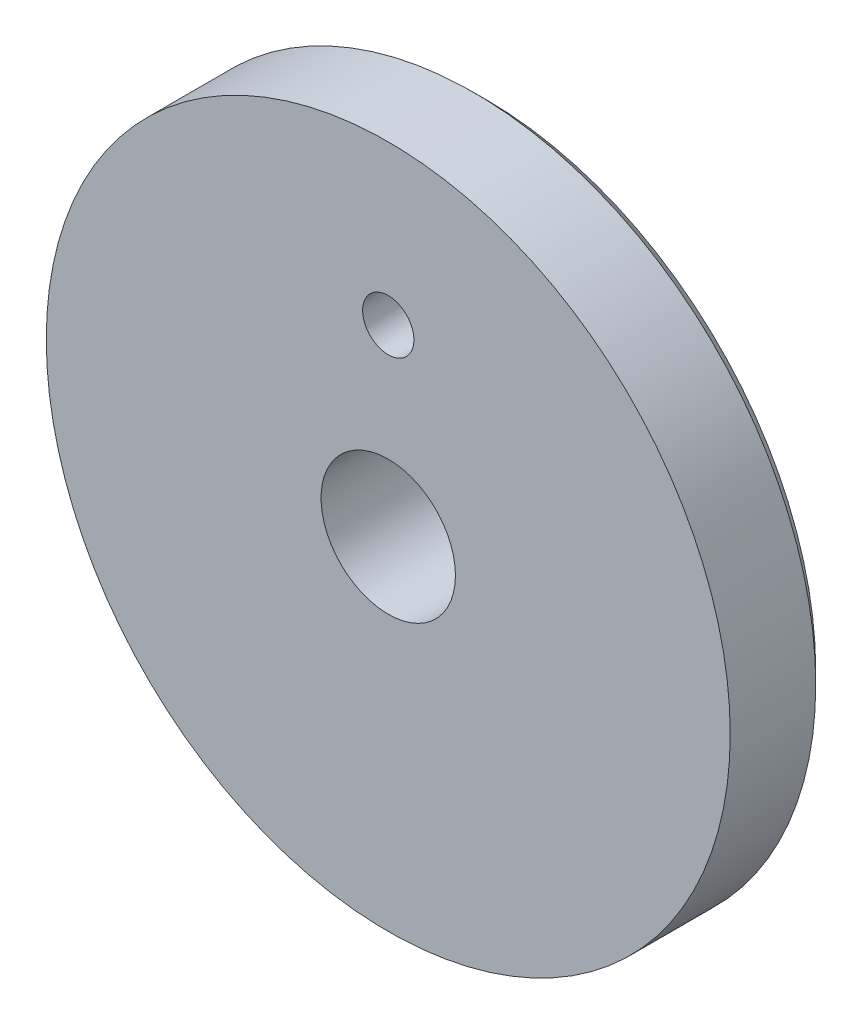
SolidWorks part; units mm, degrees
ref_plane "Front" through (0, 0, 0) normal (0, 0, 1) x (1, 0, 0)
ref_plane "Top" through (0, 0, 0) normal (0, 1, 0) x (1, 0, 0)
ref_plane "Right" through (0, 0, 0) normal (1, 0, 0) x (0, 0, -1)
sketch "Sketch1" plane through (0, 0, 0) normal (0, 0, 1) x (1, 0, 0)
  circle A0 centre (0, 0) radius 14
  circle A1 centre (0, 0) radius 2.75
  dimension "d" = 5.5
  dimension "D0" = 28
extrude "Base-Extrude" add sketch "Sketch1" against normal blind 4
sketch "Sketch2" plane through (7.2492, 0.3213, -4) normal (0, 0, -1) x (-1, 0, 0)
  circle A0 centre (7.2492, 7.1787) radius 1.05
  circle A1 centre (7.2492, -0.3213) radius 2.75 construction
  circle A2 centre (7.2492, -0.3213) radius 2.75 construction
  dimension "d1" = 2.1
  dimension "L" = 7.5
extrude "Hole" cut sketch "Sketch2" against normal through all
chamfer "Chamfer1" distance 0.5 angle 45 1 edges at (14, 0, -4)
